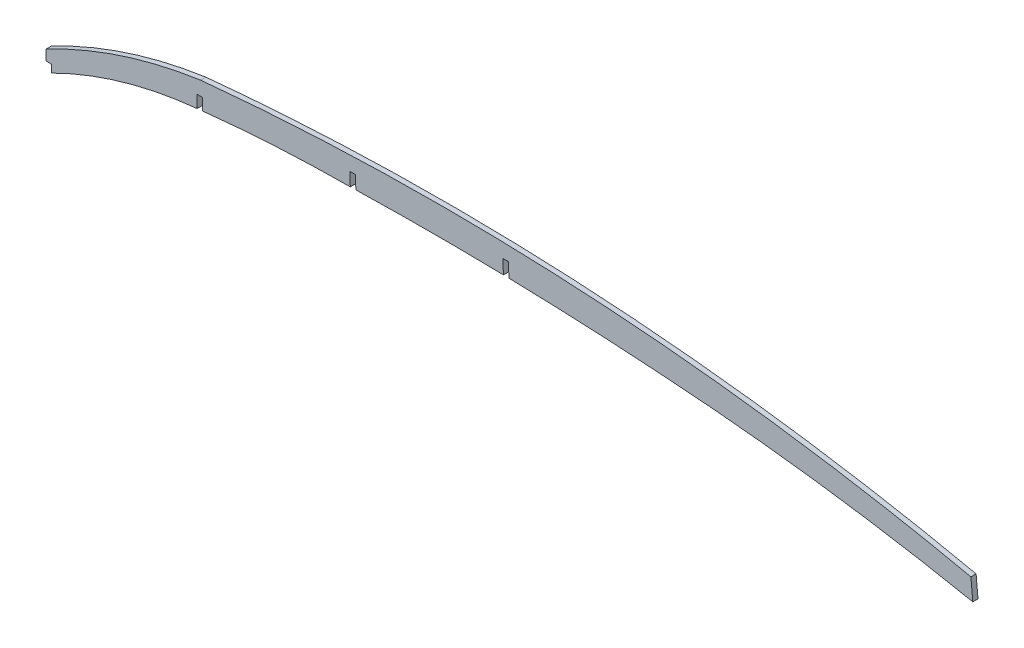
SolidWorks part; units mm, degrees
material "Plywood"
ref_plane "Front Plane" through (0, 0, 0) normal (0, 0, 1) x (1, 0, 0)
ref_plane "Top Plane" through (0, 0, 0) normal (0, 1, 0) x (1, 0, 0)
ref_plane "Right Plane" through (0, 0, 0) normal (1, 0, 0) x (0, 0, -1)
sketch "Sketch1" plane through (0, 0, 0) normal (0, 0, 1) x (1, 0, 0)
  line L0 (0, 85.9425) -> (0, 98.6503)
  line L1 (566.0852, 89.3165) -> (564.9321, 101.9675)
  arc A6 (0, 85.9425) -> (92.3925, 113.3646) centre (117.1549, -139.4255) cw
  arc A7 (92.3925, 113.3646) -> (185.8959, 118.7316) centre (190.0181, -770.2588) cw
  arc A8 (0, 98.6503) -> (94.4926, 129.4761) centre (136.5172, -159.585) cw
  arc A9 (185.8959, 118.7316) -> (373.1011, 114.6803) centre (236.8429, -1854.3326) cw
  arc A10 (373.1011, 114.6803) -> (566.0852, 89.3165) centre (283.2319, -1315.9598) cw
  spline S6 degree 3 poles (2840.1742, -3011.9753) (2207.2857, -1054.6085) (1410.1047, -9.0147) (438.4396, 123.9347) (428.6248, 125.1803) (408.999, 127.4768) (399.1847, 128.5284) (369.7378, 131.3944) (350.1011, 132.9205) (291.1746, 136.3531) (251.8686, 137.116) (-696.3591, 118.7734) (-1616.8272, -712.5738) (-2553.4552, -2680.6967) knots -5.888628 -5.888628 -5.888628 -5.888628 0.25 0.25 0.3125 0.3125 0.375 0.375 0.5 0.5 0.75 0.75 6.527741 6.527741 6.527741 6.527741 only from (564.9321, 101.9675) to (94.4926, 129.4761)
  spline S7 degree 3 poles (564.9321, 101.9675) (526.3055, 110.3591) (487.4057, 117.2349) (438.4396, 123.9347) (428.6248, 125.1803) (408.999, 127.4768) (399.1847, 128.5284) (369.7378, 131.3944) (350.1011, 132.9205) (291.1746, 136.3531) (251.8686, 137.116) (173.2133, 135.5945) (133.864, 133.3102) (94.4926, 129.4761) knots 0 0 0 0 0.25 0.25 0.3125 0.3125 0.375 0.375 0.5 0.5 0.75 0.75 1 1 1 1
  dimension "D4" = 92.3925
  dimension "D2" = 254
  dimension "D8" = 187.2051
  dimension "D9" = 28.7378
  dimension "D1" = 292.1
  dimension "D3" = 889
  dimension "D10" = 1973.7219
  dimension "D11" = 1433.46
  dimension "D5" = 27.4221
  dimension "D6" = 93.5034
  dimension "D7" = 32.7892
extrude "Boss-Extrude1" add sketch "Sketch1" against normal mid plane 3.175 contours L1 S7 A8 L0 A6 A7 A9 A10 region at (279.3924, 119.3666, 0)
sketch "Sketch2" plane through (0, 0, 1.5875) normal (0, 0, 1) x (1, 0, 0)
  line L0 (0, 0.1991) -> (0, 85.9425) construction
  line L1 (0, 49.7106) -> (0, -49.3123) construction
  line L2 (0, 0.1991) -> (93.98, 0.1991) construction
  line L3 (0, 85.9425) -> (3.3528, 85.9425)
  line L4 (0, 85.9425) -> (0, 92.3687)
  line L5 (0, 92.3687) -> (3.3528, 92.3687)
  line L6 (3.3528, 85.9425) -> (3.3528, 92.3687)
  line L7 (93.98, 0.1991) -> (93.98, 114.6261) construction
  line L8 (93.98, 114.6261) -> (93.98, 120.9849) construction
  line L9 (92.2909, 120.9087) -> (95.6691, 120.9087)
  line L10 (92.2909, 120.9087) -> (92.2909, 108.2087)
  line L11 (92.2909, 108.2087) -> (95.6691, 108.2087)
  line L12 (95.6691, 120.9087) -> (95.6691, 108.2087)
  line L14 (187.3715, 126.8935) -> (185.1806, 126.8477) construction
  line L19 (187.3715, 126.8935) -> (190.0239, 0.1991) construction
  line L20 (93.98, 0.1991) -> (190.0239, 0.1991) construction
  line L21 (185.6844, 126.782) -> (189.0619, 126.8527)
  line L22 (185.6844, 126.782) -> (185.9502, 114.0848)
  line L23 (189.0619, 126.8527) -> (189.3277, 114.1555)
  line L24 (185.9502, 114.0848) -> (189.3277, 114.1555)
  line L25 (190.0239, 0.1991) -> (671.0247, 0.1991) construction
  line L29 (279.0238, 127.4161) -> (282.3988, 127.5613)
  line L35 (279.0238, 127.4161) -> (279.5699, 114.7278)
  line L36 (280.708, 127.5648) -> (286.1898, 0.1991) construction
  line L37 (282.3988, 127.5613) -> (282.9449, 114.8731)
  line L38 (279.5699, 114.7278) -> (282.9449, 114.8731)
  point P9 (93.98, 108.2087)
  point P14 (187.3731, 126.8174)
  point P24 (280.7113, 127.4887)
  dimension "D1" = 85.7434
  dimension "D2" = 6.4262
  dimension "D3" = 3.3528
  dimension "D4" = 93.98
  dimension "D5" = 114.427
  dimension "D6" = 6.3588
  dimension "D7" = 0.0762
  dimension "D8" = 3.3782
  dimension "D9" = 96.0439
  dimension "D10" = 88.801
  dimension "D11" = 126.7222
  dimension "D12" = 0.0762
  dimension "D13" = 3.3782
  dimension "D14" = 12.7
  dimension "D15" = 12.7
  dimension "D16" = 87.536
  dimension "D17" = 96.166
  dimension "D18" = 127.4836
  dimension "D19" = 0.0762
  dimension "D20" = 3.3782
  dimension "D21" = 12.7
extrude "Cut-Extrude1" cut sketch "Sketch2" against normal through all
equation "\"slotwidth\"=0.167708"
